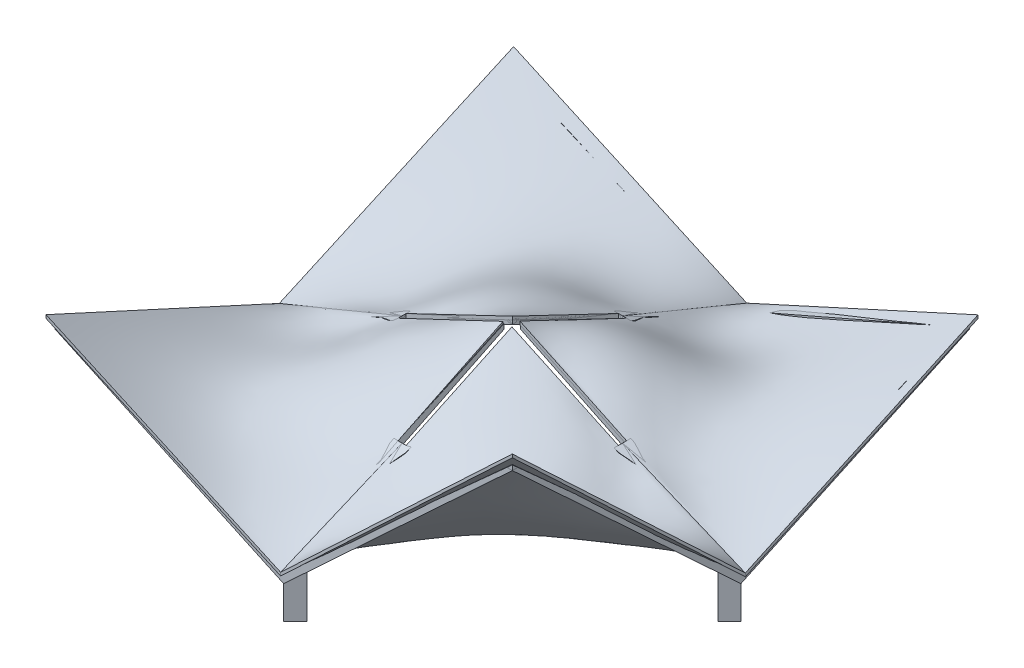
SolidWorks part; units mm, degrees
note: '?' marks a value the reader was unsure of.
other "Luz del sol"
other "Cámara1"
ref_plane "Alzado" through (0, 0, 0) normal (0, 0, 1) x (1, 0, 0)
ref_plane "Planta" through (0, 0, 0) normal (0, 1, 0) x (1, 0, 0)
ref_plane "Vista lateral" through (0, 0, 0) normal (1, 0, 0) x (0, 0, -1)
sketch "Planta " plane through (0, 0, 0) normal (0, 1, 0) x (1, 0, 0)
  line L0 (0, 0) -> (0, -14107.1068) construction
  line L1 (-14000, -14000) -> (14000, -14000) construction
  line L2 (-14000, -14000) -> (-14000, 14000) construction
  line L3 (-14000, 14000) -> (14000, 14000) construction
  line L4 (14000, -14000) -> (14000, 14000) construction
  line L5 (-14000, -14000) -> (14000, 14000) construction
  line L6 (-14000, 14000) -> (14000, -14000) construction
  line L7 (-14000, 0) -> (0, 0) construction
  line L8 (0, 0) -> (0, 14000) construction
  line L9 (0, 0) -> (14000, 0) construction
  line L10 (-7000, 0) -> (-7000, -14000) construction
  line L11 (7000, 0) -> (7000, -14000) construction
  line L12 (-7000, 0) -> (-7000, 14000) construction
  line L13 (7000, 0) -> (7000, 14000) construction
  line L14 (-13600, -250) -> (-7750, -250) construction
  line L15 (0, -250) -> (6750, -250) construction
  line L16 (-13600, 250) -> (-7750, 250) construction
  line L17 (250, 250) -> (6750, 250) construction
  line L18 (-14000, 250) -> (0, 250) construction
  line L19 (6750, 250) -> (6750, -250) construction
  line L20 (-6750, 250) -> (-6750, -250) construction
  line L21 (7750, -250) -> (7000, -500) construction
  line L22 (-13600, 13600) -> (-250, 13600) construction
  line L23 (13600, -13600) -> (13600, 13600) construction
  line L24 (-13600, -13600) -> (-250, -13600) construction
  line L25 (-13600, -13600) -> (-13600, 13600) construction
  line L26 (-7000, 500) -> (-500, 500) construction
  line L27 (-7750, 250) -> (-7000, 500) construction
  line L28 (-7000, -500) -> (-500, -500) construction
  line L29 (-7750, -250) -> (-7000, -500) construction
  line L30 (-14000, -250) -> (0, -250) construction
  line L31 (7750, 250) -> (7000, 500) construction
  line L32 (-7750, 13600) -> (-7750, 250) construction
  line L33 (7750, 250) -> (13600, 250) construction
  line L34 (-6750, 250) -> (-250, 250) construction
  line L35 (-6750, -250) -> (0, -250) construction
  line L36 (0, 250) -> (14000, 250) construction
  line L37 (7750, -250) -> (13600, -250) construction
  line L38 (0, -250) -> (14000, -250) construction
  line L39 (-250, 13600) -> (-250, 7750) construction
  line L40 (250, 13600) -> (250, 7750) construction
  line L41 (500, 7000) -> (500, 500) construction
  line L42 (250, 7750) -> (500, 7000) construction
  line L43 (-250, 7750) -> (-500, 7000) construction
  line L44 (-500, 7000) -> (-500, 500) construction
  line L45 (250, -6750) -> (-250, -6750) construction
  line L46 (250, -7750) -> (500, -7000) construction
  line L47 (-250, -7750) -> (-500, -7000) construction
  line L48 (-250, -7750) -> (-250, -13600) construction
  line L49 (250, -7750) -> (250, -13600) construction
  line L50 (250, 6750) -> (250, 250) construction
  line L51 (-250, 6750) -> (-250, 250) construction
  line L52 (250, 6750) -> (-250, 6750) construction
  line L53 (250, -250) -> (250, -6750) construction
  line L54 (-250, -250) -> (-250, -6750) construction
  line L55 (500, -500) -> (500, -7000) construction
  line L56 (500, -500) -> (7000, -500) construction
  line L57 (500, 500) -> (7000, 500) construction
  line L58 (-7750, -250) -> (-7750, -13600) construction
  line L59 (-500, -500) -> (-500, -7000) construction
  line L60 (7750, 13600) -> (7750, 250) construction
  line L61 (7750, -250) -> (7750, -13600) construction
  line L62 (250, -13600) -> (13600, -13600) construction
  line L64 (250, 13600) -> (13600, 13600) construction
  line L68 (0, -14107.1068) -> (0, -14733.2042) construction
  line L70 (-674.6212, -13432.4856) -> (-674.6212, -14733.2042) construction
  line L71 (674.6212, -13432.4856) -> (674.6212, -14733.2042) construction
  line L72 (-674.6212, -14733.2042) -> (674.6212, -14733.2042) construction
  line L77 (-674.6212, -14107.1068) -> (-674.6212, -14733.2042) construction
  line L78 (674.6212, -14107.1068) -> (674.6212, -14733.2042) construction
  line L83 (707.1068, 13292.8932) -> (0, 14000)
  line L84 (0, 12585.7864) -> (707.1068, 13292.8932)
  line L85 (-707.1068, 13292.8932) -> (0, 12585.7864)
  line L86 (0, 14000) -> (-707.1068, 13292.8932)
  line L99 (13292.8932, 707.1068) -> (12585.7864, 0)
  line L100 (12585.7864, 0) -> (13292.8932, -707.1068)
  line L101 (13292.8932, -707.1068) -> (14000, 0)
  line L102 (14000, 0) -> (13292.8932, 707.1068)
  line L104 (-13400, -13400) -> (-13400, 13400) construction
  line L105 (-13400, 13400) -> (13400, 13400) construction
  line L106 (13400, -13400) -> (13400, 13400) construction
  line L107 (-13400, -13400) -> (13400, -13400) construction
  line L111 (0, -14000) -> (-707.1068, -13292.8932)
  line L112 (-13432.4856, 674.6212) -> (-14733.2042, 674.6212) construction
  line L113 (-13432.4856, -674.6212) -> (-14733.2042, -674.6212) construction
  line L114 (-14733.2042, 674.6212) -> (-14733.2042, -674.6212) construction
  line L119 (-707.1068, -13292.8932) -> (0, -12585.7864)
  line L120 (-14000, 0) -> (-13292.8932, 707.1068)
  line L121 (-13292.8932, 707.1068) -> (-12585.7864, 0)
  line L122 (-12585.7864, 0) -> (-13292.8932, -707.1068)
  line L123 (-13292.8932, -707.1068) -> (-14000, 0)
  line L124 (0, -12585.7864) -> (707.1068, -13292.8932)
  line L125 (707.1068, -13292.8932) -> (0, -14000)
  point P0 (0, 0)
  point P64 (0, 0)
  point P100 (-12939.3398, 353.5534)
  point P101 (12939.3398, 353.5534)
  point P112 (-53.5534, -96.4466)
  dimension "D1" = 28000
  dimension "D2" = 28000
  dimension "D5" = 1000
  dimension "D7" = 5850
  dimension "D10" = 500
  dimension "D11" = 18.435
  dimension "D12" = 18.435
  dimension "D8" = 1000
  dimension "D9" = 1000
  dimension "D15" = 200
  dimension "D16" = 1000
  dimension "D18" = 1000
  dimension "D22" = 400
  dimension "D23" = 13350
  dimension "D17" = 1000
  dimension "D19" = 1000
  dimension "D3" = 250
  dimension "D4" = 250
  dimension "D6" = 2
ref_plane "ABC" through (0, 0, 14000) normal (0, 0, 1) x (1, 0, 0)
ref_plane "123" through (14000, 0, 0) normal (1, 0, 0) x (0, 0, -1)
sketch "V Borde" plane through (0, 0, 14000) normal (0, 0, 1) x (1, 0, 0)
  line L7 (-16060.9825, 0) -> (13713.4812, 0) construction
  line L9 (-14000.0895, 2000) -> (14000.0895, 2000) construction
  line L10 (-14000, 8500) -> (13713.4812, 8500) construction
  line L11 (0, 0) -> (0, 10906.2148) construction
  line L14 (250, 0) -> (250, 8500) construction
  line L15 (-250, 0) -> (-250, 8500) construction
  line L16 (-250, 0) -> (-250, 10906.2148) construction
  line L18 (250, 0) -> (250, 10906.2148) construction
  line L19 (-14000, 8800) -> (13713.4812, 8800) construction
  line L20 (-250, 8500) -> (-250, 8800)
  line L27 (250, 8500) -> (250, 8800)
  dimension "D5" = 250
  dimension "D2" = 2000
  dimension "D8" = 300
  dimension "D1" = 6500
  dimension "D6" = 250
ref_plane "Plano4" through (0, 0, 250) normal (0, 0, 1) x (1, 0, 0)
sketch "Croquis5" plane through (0, 0, 250) normal (0, 0, 1) x (1, 0, 0)
  line L0 (55, 0) -> (-55, 0) construction
  line L1 (-13600.0895, 2000) -> (-13000.0895, 2000)
  line L2 (-13000.0895, 2000) -> (-13000.0895, 2150)
  line L3 (-13000.0895, 2150) -> (-13100.0895, 2150)
  line L4 (-13100.0895, 2150) -> (-13100.0895, 2100)
  line L5 (14000, -16097.6815) -> (14000, 16097.6815) construction
  line L6 (-13100.0895, 2100) -> (-13394.7035, 2100)
  line L7 (-13600.0895, 2700) -> (-7750, 5373.0567)
  line L8 (-7750, 5373.0567) -> (-7750, 4848.3391)
  line L13 (14000.0895, 2700) -> (13600.0895, 2700) construction
  line L14 (14000.0895, 2000) -> (14000.0895, 2700) construction
  line L15 (7750, 4848.3391) -> (13394.7035, 2100) construction
  line L16 (7750, 4848.3391) -> (7750, 5373.0567) construction
  line L17 (13600.0895, 2700) -> (7750, 5373.0567) construction
  line L18 (-7750, 4848.3391) -> (-7750, 5373.0567) construction
  line L19 (-13600.0895, 2000) -> (-14000.0895, 2000) construction
  line L20 (-7750, 4848.3391) -> (-13394.7035, 2100) construction
  line L21 (-13600.0895, 2700) -> (-7750, 5373.0567) construction
  line L22 (-14000.0895, 2700) -> (-13600.0895, 2700) construction
  line L24 (-14000, 0) -> (14000, 0) construction
  line L26 (-14000, 0) -> (14000, 0) construction
  line L27 (-14000, 0) -> (13999.6225, 0) construction
  line L28 (-14000, 0) -> (14000, 0) construction
  line L29 (-7750, 4848.3391) -> (-13394.7035, 2100)
  line L30 (7750, 5373.0567) -> (7750, 4848.3391)
  line L31 (7750, 4848.3391) -> (13394.7035, 2100)
  line L35 (13600.0895, 2700) -> (7750, 5373.0567)
  line L37 (-0.1888, 0) -> (-0.1888, 13652.5647) construction
  line L38 (13099.712, 2100) -> (13394.7035, 2100)
  line L39 (13099.712, 2150) -> (13099.712, 2100)
  line L40 (12999.712, 2150) -> (13099.712, 2150)
  line L41 (12999.712, 2000) -> (12999.712, 2150)
  line L42 (12999.712, 2000) -> (13600.0895, 2000)
  line L43 (-13600.0895, 2700) -> (-13600.0895, 2000)
  line L44 (13600.0895, 2700) -> (13600.0895, 2000)
  point P0 (13600.0895, 2700)
  dimension "D1" = 2000
  dimension "D2" = 700
  dimension "D3" = 114.557
  dimension "D4" = 15500
  dimension "D5" = 6250.0895
  dimension "D6" = 6431.8566
  dimension "D7" = 700
  dimension "D8" = 524.7176
  dimension "D9" = 524.7176
  dimension "D10" = 4848.3391
  dimension "D11" = 4848.3391
  dimension "D12" = 400
  dimension "D13" = 400
  dimension "D14" = 400
  dimension "D15" = 400
  dimension "D16" = 7750
  dimension "D17" = 27999.6225
  dimension "D18" = 14000
  dimension "D19" = 600
  dimension "D20" = 100
  dimension "D21" = 100
  dimension "D22" = 50
  dimension "D23" = 25.961
  dimension "D24" = 25.961
  dimension "D25" = 294.9915
  dimension "D26" = 6431.8566
  dimension "D27" = 600.3775
extrude "V Central" add sketch "Croquis5" against normal blind 500
ref_plane "Plano6" through (0, 0, 500) normal (0, 0, 1) x (1, 0, 0)
sketch "V Central Cenital" plane through (0, 0, 500) normal (0, 0, 1) x (1, 0, 0)
  line L7 (-14000, 0) -> (14000, 0) construction
  line L8 (7000, 5213.5052) -> (7000, 5715.751)
  line L9 (250, 8500) -> (7000, 5213.5052)
  line L10 (7000, 5715.751) -> (250, 8800)
  line L11 (250, 8500) -> (250, 8800)
  line L12 (-250, 8500) -> (-250, 8800)
  line L13 (-250, 8500) -> (-7000, 5213.5052)
  line L14 (-7000, 5213.5052) -> (-7000, 5715.751)
  line L15 (-7000, 5715.751) -> (-250, 8800)
  line L16 (-14000, 0) -> (14000, 0) construction
  line L19 (0, 0) -> (0, 10906.2148) construction
  dimension "D1" = 6750
  dimension "D2" = 6750
  dimension "D3" = 8800
  dimension "D4" = 8800
  dimension "D5" = 5715.751
  dimension "D6" = 5715.751
  dimension "D7" = 5213.5052
  dimension "D8" = 5213.5052
  dimension "D9" = 8500
  dimension "D10" = 8500
  dimension "D11" = 250
  dimension "D12" = 250
extrude "Saliente-Extruir2" add sketch "V Central Cenital" against normal blind 1000 separate body
sketch "Hueco" plane through (0, 0, 0) normal (0, 1, 0) x (1, 0, 0)
  line L1 (-6750, -250) -> (6750, -250)
  line L2 (-6750, -250) -> (-6750, 250)
  line L3 (-6750, 250) -> (6750, 250)
  line L4 (6750, -250) -> (6750, 250)
loft "Recubrir5" add section face at (-7000, 5464.6281, 0) section face at (-7750, 5110.6979, 0) connector at (-7000, 5715.751, 500) connector at (-7750, 5373.0567, 250)
loft "Recubrir6" add section face at (7750, 5110.6979, 0) section face at (7000, 5464.6281, 0) connector at (7750, 5373.0567, 250) connector at (7000, 5715.751, 500)
extrude "Hueco cenital" cut sketch "Hueco" along normal blind 9837
sketch "Eje central" plane through (0, 0, 0) normal (0, 0, 1) x (1, 0, 0)
  line L0 (0, 0) -> (0, 10906.2148) construction
ref_axis "Eje1" through (0, 0, 0) along (0, 1, 0)?
pattern_circular "MatrizC12" count 2 every 90 about axis through (0, 0, 0) along (0, 1, 0) reverse direction yes of bodies 111 112
sketch "Croquis8" plane through (3369.6274, 7374.5618, 0) normal (0.4156, 0.9095, 0) x (0.9095, -0.4156, 0)
  line L0 (-3429.8614, -250) -> (-3155.0972, -500)
  line L1 (-3429.8614, -250) -> (-3429.8614, -500) construction
  line L2 (3991.3981, -500) -> (-3429.8614, -500) construction
  line L3 (-3155.0972, -500) -> (-3155.0972, -250)
  line L4 (3716.5366, -250) -> (-3429.8614, -250) construction
  line L5 (-3155.0972, -250) -> (-3429.8614, -250)
  line L6 (-3429.8614, 250) -> (-3154.961, 250)
  line L7 (-3429.8614, 250) -> (3716.5366, 250) construction
  line L11 (-3429.8614, 250) -> (-3154.961, 500)
  line L12 (3991.3981, 500) -> (-3429.8614, 500) construction
  line L13 (-3154.961, 500) -> (-3154.961, 250)
  dimension "D1" = 371.4772
extrude "Cortar-Extruir3" cut sketch "Croquis8" along normal blind 150
sketch "Croquis9" plane through (0, 7374.5618, 3369.6274) normal (0, 0.9095, 0.4156) x (1, 0, 0)
  line L1 (-250, -3716.5366) -> (-250, 3429.8614) construction
  line L3 (-500, -3991.3981) -> (-500, 3429.8614) construction
  line L5 (250, 3429.8614) -> (499.9115, 3155.0972)
  line L6 (250, 3429.8614) -> (499.9115, 3155.0972) construction
  line L7 (499.9115, 3155.0972) -> (250, 3155.0972)
  line L8 (250, 3429.8614) -> (250, -3716.5366) construction
  line L9 (250, 3155.0972) -> (250, 3429.8614)
  line L11 (-250, 3429.8614) -> (-500, 3154.9187)
  line L12 (-500, 3154.9187) -> (-250, 3154.9187)
  line L13 (-250, 3154.9187) -> (-250, 3429.8614)
  dimension "D1" = 371.6093
  dimension "D2" = 250
  dimension "D3" = 249.9115
extrude "Cortar-Extruir4" cut sketch "Croquis9" along normal blind 150
sketch "Croquis10" plane through (-3369.6274, 7374.5618, 0) normal (-0.4156, 0.9095, 0) x (0.9095, 0.4156, 0)
  line L0 (3429.8614, 250) -> (3155.0179, 250)
  line L1 (-3716.5366, 250) -> (3429.8614, 250) construction
  line L8 (3429.8614, -250) -> (-3716.5366, -250) construction
  line L9 (3155.0981, -250) -> (3429.8614, -250)
  line L10 (3429.8614, -250) -> (3155.0981, -500)
  line L11 (3155.0981, -500) -> (3155.0981, -250)
  line L12 (3429.8614, 250) -> (3155.0179, 500)
  line L13 (3429.8614, 500) -> (-3991.3981, 500) construction
  line L14 (3155.0179, 500) -> (3155.0179, 250)
  dimension "D1" = 371.5359
extrude "Cortar-Extruir5" cut sketch "Croquis10" along normal blind 150
sketch "Croquis11" plane through (0, 7374.5618, -3369.6274) normal (0, 0.9095, -0.4156) x (1, 0, 0)
  line L0 (250, -3429.8614) -> (250, -3154.6208)
  line L1 (250, 3716.5366) -> (250, -3429.8614) construction
  line L2 (250, -3154.6208) -> (500, -3154.6208)
  line L3 (500, -3155.0469) -> (500, 3991.3981) construction
  line L4 (500, -3154.6208) -> (250, -3429.8614)
  line L5 (-250, -3429.8614) -> (-499.9836, -3155.0179)
  line L6 (-499.9836, -3155.0179) -> (-250, -3155.0179)
  line L7 (-250, -3429.8614) -> (-250, 3716.5366) construction
  line L8 (-250, -3155.0179) -> (-250, -3429.8614)
  dimension "D1" = 371.8297
extrude "Cortar-Extruir6" cut sketch "Croquis11" along normal blind 150
sketch "Croquis12" plane through (0, 0, 14000) normal (0, 0, 1) x (1, 0, 0)
  line L0 (-14000, 8800) -> (0, 2700)
  line L1 (0, 0) -> (0, 10906.2148) construction
  line L2 (0, 2700) -> (14000.0895, 15300)
  line L4 (14000.0895, 15000) -> (0, 2000)
  line L5 (0, 2000) -> (-14000, 8500)
  line L6 (-14000, 8500) -> (-14000, 8800)
  line L8 (-14000.0895, 2000) -> (14000.0895, 2000) construction
  line L9 (14000.0895, 2000) -> (14000, 2300) construction
  line L10 (14000, -5998.4181) -> (14000, 5998.4181) construction
  line L11 (14000.0895, 15300) -> (14000.0895, 15000)
  line L12 (14000.0895, 2000) -> (14000.0895, 20808.6334) construction
  dimension "D1" = 2000
  dimension "D3" = 700
  dimension "D4" = 13000
  dimension "D5" = 300
extrude "VIGA BORDE C-1" add sketch "Croquis12" against normal blind 400
sketch3d "Eje C1"
  line L0 (14000, 0, 14000) -> (13600, 0, 13600) construction
  line L1 (13800, 0, 13800) -> (13800, 25391.5006, 13800) construction
  line L2 (-14000, 0, -14000) -> (14000, 0, 14000) construction
  line L3 (0, 0, 0) -> (0, 2700, 14000) construction
  line L4 (0, 2700, 14000) -> (14000, 2700, 14000) construction
pattern_circular "MatrizC15" count 2 every 90 about axis through (13800, 0, 13800) along (0, 1, 0) of "VIGA BORDE C-1" reverse direction yes
sketch "Croquis13" plane through (0, 1491.7212, -1342.5405) normal (0, 0.7433, -0.669) x (1, 0, 0)
  line L0 (14046.4585, -20641.2042) -> (13600, -20641.3386)
  line L1 (13600, -20641.3386) -> (13600, -20103.0748)
  line L2 (13600, -20103.0748) -> (14046.4585, -20103.0748)
  line L4 (14046.4585, -20103.0748) -> (14046.4585, -20641.2042)
extrude "Cortar-Extruir7" cut sketch "Croquis13" along normal blind 400
sketch "Croquis14" plane through (-1342.5405, 1491.7212, 0) normal (-0.669, 0.7433, 0) x (0.7433, 0.669, 0)
  line L0 (20103.0748, -13600) -> (20103.0748, -14100.5578)
  line L2 (20103.0748, -14100.5578) -> (20762.5183, -14100.5578)
  line L3 (20762.5183, -14100.5578) -> (20762.5183, -13600)
  line L4 (20762.5183, -13600) -> (20103.0748, -13600)
extrude "Cortar-Extruir8" cut sketch "Croquis14" along normal blind 400 contours L4 L0 L2 L3
ref_plane "Borde A3" through (0, 0, -14000) normal (0, 0, 1) x (1, 0, 0)
sketch "Croquis15" plane through (0, 0, -14000) normal (0, 0, 1) x (1, 0, 0)
  line L0 (-14000, 8800) -> (0, 2700)
  line L1 (0, 2700) -> (14000, 8800)
  line L2 (14000, 8800) -> (14000, 8499.9584)
  line L3 (14000, 2000) -> (14000, 14999.9169) construction
  line L4 (14000, 8499.9584) -> (0, 2000)
  line L5 (-14000.0895, 2000) -> (14000.0895, 2000) construction
  line L6 (0, 2000) -> (-14000, 8500)
  line L7 (-14000, 8500) -> (-14000, 8800)
extrude "VIGA BORDE A-3" add sketch "Croquis15" along normal blind 400
sketch3d "Eje A3"
  line L0 (-13600, 0, -13600) -> (-14000, 0, -14000) construction
  line L1 (-13800, 0, -13800) -> (-13800, 31461.018, -13800) construction
pattern_circular "MatrizC16" count 2 every 90 about axis through (-13800, 0, -13800) along (0, 1, 0) of "VIGA BORDE A-3" reverse direction yes
sketch "Croquis16" plane through (-988.7226, 2269.1994, 0) normal (-0.3994, 0.9168, 0) x (0.9168, 0.3994, 0)
  line L0 (16349.7144, 14000) -> (15913.394, 13600)
  line L1 (15913.394, 13600) -> (15913.394, 14000)
  line L2 (15913.394, 14000) -> (16349.7144, 14000)
extrude "Cortar-Extruir9" cut sketch "Croquis16" along normal blind 400
sketch "Croquis17" plane through (0, 2269.1994, 988.7226) normal (0, 0.9168, 0.3994) x (1, 0, 0)
  line L0 (14000, 15913.394) -> (14000, 16349.7144)
  line L1 (14000, 16349.7144) -> (13600, 15913.394)
  line L2 (13600, 15913.394) -> (14000, 15913.394) construction
  line L3 (13600, 15913.394) -> (14000, 15913.394)
  line L4 (13600, 1078.4997) -> (13600, 15913.394) construction
extrude "Cortar-Extruir10" cut sketch "Croquis17" along normal blind 400
sketch "Croquis18" plane through (0, 2269.1994, 988.7226) normal (0, 0.9168, 0.3994) x (1, 0, 0)
  line L0 (-14000, 16349.7144) -> (-14000, 15913.394)
  line L1 (-14000, 15913.394) -> (-13600, 15913.394)
  line L2 (-13600, 15913.394) -> (-14000, 16349.7144)
extrude "Cortar-Extruir11" cut sketch "Croquis18" along normal blind 400 contours L0 L1 L2
sketch "Croquis19" plane through (988.7226, 2269.1994, 0) normal (0.3994, 0.9168, 0) x (0.9168, -0.3994, 0)
  line L0 (-15913.394, 14000) -> (-16349.7144, 14000)
  line L1 (-16349.7144, 14000) -> (-15913.394, 13600)
  line L2 (-15913.394, 13600) -> (-15913.394, 14000)
extrude "Cortar-Extruir12" cut sketch "Croquis19" along normal blind 400 contours L1 L2 L0
sketch "Croquis20" plane through (988.7226, 2269.1994, 0) normal (0.3994, 0.9168, 0) x (0.9168, -0.3994, 0)
  line L0 (-16349.7144, -14000) -> (-15913.394, -13600)
  line L1 (-15913.394, -13600) -> (-15913.394, -14000)
  line L2 (-1078.4997, -14000) -> (-15913.394, -14000) construction
  line L3 (-15913.394, -14000) -> (-16349.7144, -14000)
extrude "Cortar-Extruir13" cut sketch "Croquis20" along normal blind 400 contours L3 L0 L1
sketch "Croquis21" plane through (0, 2269.1994, -988.7226) normal (0, 0.9168, -0.3994) x (1, 0, 0)
  line L0 (-14000, -15830.0761) -> (-14000, -16349.7144)
  line L1 (-14000, -16349.7144) -> (-13600, -15913.394)
  line L2 (-13600, -15913.394) -> (-13600, -1078.4997) construction
  line L4 (-14000, -15830.0761) -> (-13600, -15830.0761)
  line L5 (-13600, -15830.0761) -> (-13600, -15913.394)
  line L6 (0, -13913.1041) -> (-14000, -16349.7144) construction
  line L7 (-14000, -15913.394) -> (-14000, -1078.4997) construction
  line L8 (-13600, -15913.394) -> (-13600, -1078.4997) construction
  line L9 (-13600, -15913.394) -> (-14000, -15913.394) construction
extrude "Cortar-Extruir14" cut sketch "Croquis21" along normal blind 400
extrude "Saliente-Extruir6" add sketch "Planta " along normal blind 2700 separate body contours L111
sketch "Plano de planta" plane through (0, 0, 0) normal (0, 1, 0) x (1, 0, 0)
  line L0 (0, 0) -> (14000, 0) construction
  line L1 (-14000, -14000) -> (14000, -14000) construction
  line L2 (-14000, -14000) -> (-14000, 14000) construction
  line L5 (-13600, 13600) -> (13600, 13600) construction
  line L6 (-13600, 13600) -> (-13600, -13600) construction
  line L7 (-13600, -13600) -> (13600, -13600) construction
  line L8 (13600, 13600) -> (13600, -13600) construction
  line L9 (0, 0) -> (0, 14000) construction
  line L10 (-13600, 250) -> (-7750, 250) construction
  line L11 (-7750, 250) -> (-7000, 500) construction
  line L12 (-7000, 500) -> (-500, 499.905) construction
  line L13 (-500, 499.905) -> (-500, 7000) construction
  line L14 (-500, 7000) -> (-250, 7750) construction
  line L15 (-250, 7750) -> (-250, 13600) construction
  line L16 (250, 13600) -> (250, 7750) construction
  line L17 (250, 7750) -> (500, 7000) construction
  line L18 (500, 7000) -> (500, 499.9647) construction
  line L19 (500, 499.9647) -> (7000, 500) construction
  line L20 (7000, 500) -> (7750, 250) construction
  line L21 (7750, 250) -> (13600, 250) construction
  line L22 (13600.0895, 250) -> (7750, 250) construction
  line L23 (13600, 250) -> (13600, -250) construction
  line L24 (13600, -250) -> (7750, -250) construction
  line L25 (7750, -250) -> (7000, -500) construction
  line L26 (7000, -500) -> (500, -499.4876) construction
  line L27 (500, -499.4876) -> (500, -7000) construction
  line L28 (500, -7000) -> (250, -7750) construction
  line L29 (250, -7750) -> (250, -13600) construction
  line L30 (250, -13600) -> (-250, -13600) construction
  line L31 (-250, -13600) -> (-250, -7750) construction
  line L32 (-250, -7750) -> (-500, -7000) construction
  line L33 (-500, -7000) -> (-500, -499.4831) construction
  line L34 (-500, -499.4831) -> (-7000, -500) construction
  line L35 (-7000, -500) -> (-7750, -250) construction
  line L36 (-7750, -250) -> (-13600, -250) construction
  line L37 (-7750, -250) -> (-13600.0895, -250) construction
  line L39 (-6750, 250) -> (-6750, -250) construction
  line L40 (-6750, -250) -> (-250, -250) construction
  line L41 (-250, -250) -> (-250, -6750) construction
  line L42 (-250, -6750) -> (250, -6750) construction
  line L43 (250, -6750) -> (250, -250) construction
  line L44 (250, -250) -> (6750, -250) construction
  line L45 (6750, -250) -> (6750, 250) construction
  line L46 (6750, 250) -> (250, 250) construction
  line L47 (250, 250) -> (250, 6750) construction
  line L48 (250, 6750) -> (-250, 6750) construction
  line L49 (-250, 6750) -> (-250, 250) construction
  line L50 (-250, 250) -> (-6750, 250) construction
  line L52 (-14000, 14000) -> (14000, 14000) construction
  line L53 (14000, 14000) -> (14000, -14000) construction
  line L54 (0, 0) -> (0, -14000) construction
  line L55 (0, 0) -> (-13600, 0) construction
  dimension "D1" = 28000
  dimension "D2" = 400
sketch3d "Croquis3D1"
  line L23 (6750, 5829.9825, 250) -> (6750, 5829.9825, 0)
  line L26 (250, 5829.9825, 6750) -> (-250, 5829.9825, 6750) construction
  line L27 (0, 5829.9825, 6750) -> (250, 5829.9825, 6750)
  line L29 (0, 5829.9825, 6750) -> (0, 2699.9733, 14186.4645)
  line L33 (6750, 5829.9825, -250) -> (6750, 5829.9825, 250) construction
  line L37 (6750, 5829.9825, 0) -> (14270.0254, 2700.5087, 0)
  line L40 (250, 5829.9825, 6750) -> (287.043, 8919.8721, 310.029)
  line L41 (287.043, 8919.8721, 310.029) -> (6750, 5829.9825, 250)
  line L52 (14270.0254, 2700.5087, 0) -> (14176.0677, 16055.1213, 14175.8728)
  line L53 (14176.0677, 16055.1213, 14175.8728) -> (0, 2699.9733, 14186.4645)
surface "Parabolide BC-12" sketch "Croquis3D1"
sketch3d "Croquis3D2"
  line L21 (-285.5309, 8911.663, 285.5309) -> (-250, 5829.9825, 6750)
  line L22 (-250, 5829.9825, 6750) -> (-0.0001, 5829.9827, 6749.9999)
  line L23 (-0.0001, 5829.9827, 6749.9999) -> (0, 2699.9734, 14186.4645)
  line L24 (0, 2699.9734, 14186.4645) -> (-14278.0566, 9267.6909, 14278.0566)
  line L28 (-14268.347, 2730.3794, 0) -> (-6750, 5829.9825, 0)
  line L29 (-6750, 5829.9825, 250) -> (-6750, 5829.9825, -250) construction
  line L30 (-6750, 5829.9825, 0) -> (-6750, 5829.9825, 250)
  line L31 (-6750, 5829.9825, 250) -> (-285.5309, 8911.663, 285.5309)
  line L32 (-14278.0566, 9267.6909, 14278.0566) -> (-14268.347, 2730.3794, 0)
surface "Paraboloide AB-12" sketch "Croquis3D2"
sketch3d "Croquis3D3"
  line L22 (-0.0939, 2700.0409, -14360.379) -> (0, 5829.9825, -6750)
  line L23 (-250, 5829.9825, -6750) -> (250, 5829.9825, -6750) construction
  line L24 (0, 5829.9825, -6750) -> (-250, 5829.9825, -6750)
  line L25 (-250, 5829.9825, -6750) -> (-250, 8937.0912, -250)
  line L26 (-250, 8937.0912, -250) -> (-6750, 5829.9825, -250)
  line L27 (-6750, 5829.9825, -250) -> (-6750, 5829.9824, 0)
  line L28 (-6750, 5829.9824, 0) -> (-14268.347, 2730.3794, 0)
  line L30 (-14268.347, 2730.3794, 0) -> (-14205.9273, 9237.9541, -14284.9283)
  line L31 (-14205.9273, 9237.9541, -14284.9283) -> (-0.0939, 2700.0409, -14360.379)
surface "Paraboloide AB-23" sketch "Croquis3D3"
sketch3d "Croquis3D4"
  line L1 (227.3398, 8927.2024, -233.2793) -> (250, 5829.9825, -6750)
  line L25 (-0.0939, 2700.0407, -14360.3791) -> (0, 5829.9818, -6750)
  line L29 (0, 5829.9818, -6750) -> (250, 5829.9825, -6750)
  line L30 (-0.0939, 2700.0407, -14360.3791) -> (14263.5637, 9262.097, -14255.9505)
  line L31 (14263.5637, 9262.097, -14255.9505) -> (14270.0254, 2700.5086, 0)
  line L32 (6750, 5829.9825, -250) -> (227.3398, 8927.2024, -233.2793)
  line L36 (14270.0254, 2700.5086, 0) -> (6749.9999, 5829.9828, -0.0001)
  line L37 (6749.9999, 5829.9828, -0.0001) -> (6750, 5829.9825, -250)
surface "Paraboloide BC-23" sketch "Croquis3D4"
ref_axis "Eje2" through (0, 0, 0) along (0, 1, 0)?
ref_axis "Eje3" through (0, 2700, -14107.1068) along (0, -1, 0)?
ref_plane "Plano8" through (0, 0, 0) normal (-1, 0, 0) x (0, 0, 1)
ref_plane "Plano13" through (0, 0, 0) normal (0.7071, 0, -0.7071) x (-0.7071, 0, -0.7071)
move or copy body "Sólido-Mover/Copiar5" bodies to move or copy 156 157 158 155 copy yes number of copies 1 translate (0, -200, 0)
sketch3d "Croquis3D6"
  line L0 (0, 2499.9734, 14186.4645) -> (14176.0677, 15855.1213, 14175.8728)
  line L3 (14263.5637, 9062.0971, -14255.9505) -> (-0.0939, 2500.0407, -14360.3791)
  line L4 (-0.0939, 2500.0407, -14360.3791) -> (-14205.9273, 9037.9541, -14284.9283)
  line L5 (-14205.9273, 9037.9541, -14284.9283) -> (-14268.347, 2530.3794, 0)
  line L6 (-14268.347, 2530.3794, 0) -> (-14278.0566, 9067.6909, 14278.0566)
  line L7 (-14278.0566, 9067.6909, 14278.0566) -> (0, 2499.9734, 14186.4645)
  line L9 (14263.5637, 9062.0971, -14255.9505) -> (14270.0254, 2500.5086, 0)
  line L10 (14176.0677, 15855.1213, 14175.8728) -> (14270.0254, 2500.5086, 0)
  spline S0 degree 3 poles (14176.0677, 15855.1213, 14175.8728) (14191.7273, 13629.3525, 11813.2274) (14207.3869, 11403.5838, 9450.5819) (14238.7079, 6952.0394, 4725.2927) (14254.3619, 4726.2922, 2362.6415) (14270.0254, 2500.5086, 0) knots 0 0 0 0 0.5 0.5 1 1 1 1 construction
  spline S1 degree 3 poles (-0.0939, 2500.0416, -14360.379) (148.4859, 2568.3936, -14359.2913) (297.0657, 2636.7499, -14358.2035) (594.2252, 2773.4603, -14356.0278) (742.805, 2841.8151, -14354.94) (1188.5443, 3046.8785, -14351.6767) (1485.7038, 3183.5874, -14349.5011) (2080.0229, 3457.0081, -14345.1499) (2377.1824, 3593.7162, -14342.9743) (2971.5015, 3867.1348, -14338.6231) (3268.661, 4003.8458, -14336.4475) (4754.4587, 4687.3909, -14325.5696) (5943.0968, 5234.2318, -14316.8671) (9509.0112, 6874.7451, -14290.76) (11886.2876, 7968.4161, -14273.3553) (14263.5637, 9062.0971, -14255.9505) knots 0 0 0 0 0.03125 0.03125 0.0625 0.0625 0.125 0.125 0.1875 0.1875 0.25 0.25 0.5 0.5 1 1 1 1 construction
  dimension "D1" = 15693.5212
surface "Superficie-Extruir1" sketch "Plano de planta" parameters "D1"=200
sketch3d "Croquis3D9" plane through (0, 0, 0) normal (0, 0, 1) x (1, 0, 0)
sketch3d "Croquis3D10"
  line L0 (-14268.347, 2730.3792, 0) -> (-14278.0566, 9267.6909, 14278.0566)
  line L1 (-14278.0566, 9267.6909, 14278.0566) -> (0, 2699.9734, 14186.4645)
  line L2 (0, 2699.9734, 14186.4645) -> (14176.0677, 16055.1213, 14175.8728)
  line L3 (14176.0677, 16055.1213, 14175.8728) -> (14270.0254, 2700.5087, 0)
  line L4 (14270.0254, 2700.5087, 0) -> (14263.5637, 9262.0971, -14255.9505)
  line L5 (14263.5637, 9262.0971, -14255.9505) -> (-0.0939, 2700.0407, -14360.3791)
  line L6 (-0.0939, 2700.0407, -14360.3791) -> (-14205.9273, 9237.9541, -14284.9283)
  line L7 (-14205.9273, 9237.9541, -14284.9283) -> (-14268.347, 2730.3792, 0)
  spline S0 degree 3 poles (-0.0001, 5829.9827, 6749.9999) (0.0008, 5821.8283, 6769.3666) (-0.0002, 5813.6813, 6788.7313) (-0.0003, 5797.3792, 6827.4629) (-0.0001, 5789.2277, 6846.8288) (0.0002, 5764.7732, 6904.9265) (0.0003, 5748.4707, 6943.6582) (0, 5699.5655, 7059.8527) (-0.0002, 5666.9618, 7137.3157) (0.0003, 5569.1471, 7369.7057) (0, 5503.94, 7524.6317) (0.0001, 5308.3139, 7989.4109) (0, 5177.8972, 8299.2634) (-0.0001, 4786.6464, 9228.8214) (0.0004, 4525.8106, 9848.5272) (-0.0003, 4004.1448, 11087.9373) (0.0002, 3743.309, 11707.6432) (-0.0001, 3352.059, 12637.2009) (0, 3221.6417, 12947.0537) (0, 3026.0159, 13411.8328) (0, 2960.8074, 13566.7591) (-0.0002, 2830.391, 13876.6116) (0.0005, 2765.1801, 14031.5386) (0, 2699.9734, 14186.4645) knots 0 0 0 0 0.007812 0.007812 0.015625 0.015625 0.03125 0.03125 0.0625 0.0625 0.125 0.125 0.25 0.25 0.5 0.5 0.75 0.75 0.875 0.875 0.9375 0.9375 1 1 1 1 construction
  spline S1 degree 3 poles (0, 2699.9734, 14186.4645) (147.6693, 2839.0821, 14186.3561) (295.334, 2978.2085, 14186.243) (590.6695, 3256.4379, 14186.0231) (738.3368, 3395.5541, 14185.9128) (1181.339, 3812.9021, 14185.5819) (1476.6739, 4091.134, 14185.3613) (2362.6775, 4925.8329, 14184.6988) (2953.3474, 5482.2958, 14184.2579) (4725.3559, 7151.6893, 14182.9339) (5906.6949, 8264.6183, 14182.0513) (9450.7111, 11603.4079, 14179.4027) (11813.3912, 13829.2575, 14177.6397) (14176.0677, 16055.1213, 14175.8728) knots 0 0 0 0 0.03125 0.03125 0.0625 0.0625 0.125 0.125 0.25 0.25 0.5 0.5 1 1 1 1 construction
  spline S2 degree 3 poles (14270.0254, 2700.5087, 0) (13643.3567, 2961.296, 0) (13016.6878, 3222.0885, 0) (11763.3502, 3743.6665, 0) (11136.6814, 4004.4561, 0) (9883.3439, 4526.0358, 0) (9256.6751, 4786.8241, -0.0001) (8316.6719, 5178.0097, -0.0001) (8003.3375, 5308.4038, -0.0001) (7376.6687, 5569.1919, -0.0001) (7063.3342, 5699.5917, 0) (6749.9999, 5829.9825, -0.0001) knots 0 0 0 0 0.25 0.25 0.5 0.5 0.75 0.75 0.875 0.875 1 1 1 1 construction
